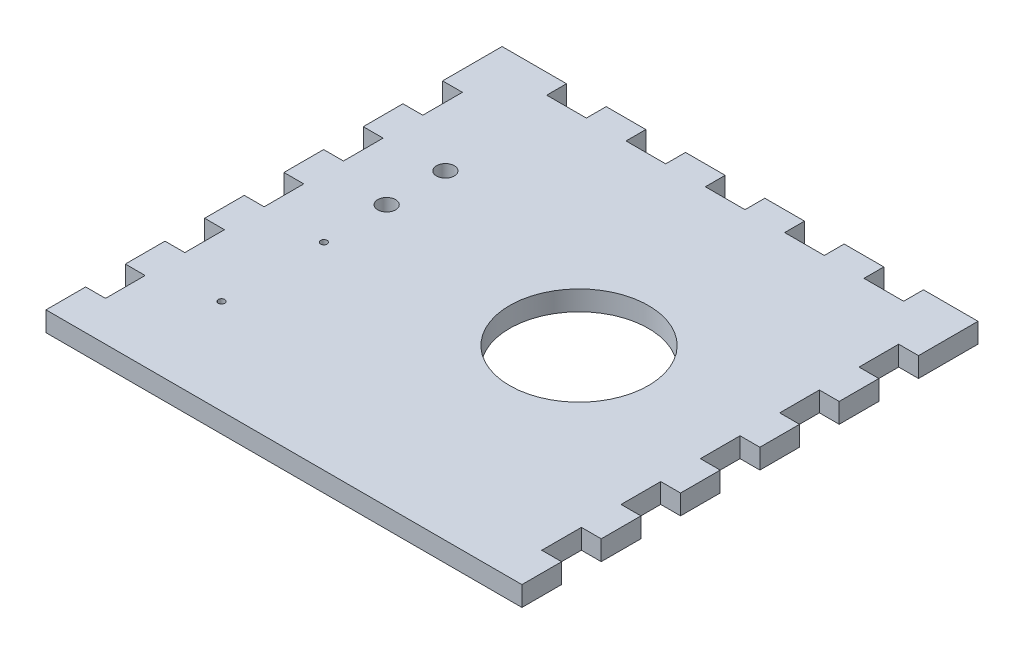
SolidWorks part; units mm, degrees
ref_plane "Front Plane" through (0, 0, 0) normal (0, 0, 1) x (1, 0, 0)
ref_plane "Top Plane" through (0, 0, 0) normal (0, 1, 0) x (1, 0, 0)
ref_plane "Right Plane" through (0, 0, 0) normal (1, 0, 0) x (0, 0, -1)
sketch "Sketch1" plane through (0, 0, 0) normal (0, 1, 0) x (1, 0, 0)
  line L1 (-139.7, -139.7) -> (139.7, -139.7)
  line L2 (-139.7, -139.7) -> (-139.7, 139.7)
  line L3 (-139.7, 139.7) -> (139.7, 139.7)
  line L4 (139.7, -139.7) -> (139.7, 139.7)
  line L5 (-139.7, -139.7) -> (139.7, 139.7) construction
  line L6 (-139.7, 139.7) -> (139.7, -139.7) construction
  point P0 (0, 0)
  dimension "D1" = 279.4
  dimension "D2" = 279.4
extrude "Boss-Extrude1" add sketch "Sketch1" along normal blind 12.7
sketch "Sketch2" plane through (139.7, 0, 0) normal (1, 0, 0) x (0, 0, -1)
  line L0 (-139.7, 12.7) -> (139.7, 12.7) construction
  line L1 (-139.7, 0) -> (-114.3, 0)
  line L2 (-139.7, 0) -> (-139.7, 12.7)
  line L3 (-139.7, 12.7) -> (-114.3, 12.7)
  line L4 (-114.3, 0) -> (-114.3, 12.7)
  dimension "D1" = 25.4
extrude "Boss-Extrude2" add sketch "Sketch2" along normal blind 12.7
pattern_linear "LPattern1" count 6 spacing 50.8 along (0, 0, -1) of "Boss-Extrude2"
mirror "Mirror1" about plane through (0, 0, 0) normal (1, 0, 0) of "LPattern1"
sketch "Sketch3" plane through (0, 0, -139.7) normal (0, 0, -1) x (-1, 0, 0)
  line L0 (-152.4, 12.7) -> (152.4, 12.7) construction
  line L1 (-142.875, 12.7) -> (-117.475, 12.7)
  line L2 (-142.875, 12.7) -> (-142.875, 0)
  line L3 (-142.875, 0) -> (-117.475, 0)
  line L4 (-117.475, 12.7) -> (-117.475, 0)
  line L5 (-152.4, 0) -> (152.4, 0) construction
  line L6 (-152.4, 0) -> (-152.4, 12.7) construction
  dimension "D1" = 9.525
  dimension "D2" = 25.4
extrude "Boss-Extrude3" add sketch "Sketch3" along normal blind 12.7
pattern_linear "LPattern2" count 6 spacing 50.8 along (-1, 0, 0) of "Boss-Extrude3"
sketch "Sketch5" plane through (0, 0, -139.7) normal (0, 0, -1) x (-1, 0, 0)
  line L6 (160.655, 0) -> (-160.655, 0) construction
  line L7 (-152.4, 12.7) -> (-135.3964, 12.7)
  line L8 (-152.4, 12.7) -> (-152.4, 0)
  line L9 (-152.4, 0) -> (-135.3964, 0)
  line L10 (-135.3964, 12.7) -> (-135.3964, 0)
extrude "Boss-Extrude4" add sketch "Sketch5" along normal blind 12.7
mirror "Mirror2" about plane through (0, 0, 0) normal (1, 0, 0) of "Boss-Extrude4"
sketch "Sketch6" plane through (0, 12.7, 0) normal (0, 1, 0) x (1, 0, 0)
  line L0 (66.675, 139.7) -> (41.275, 139.7) construction
  line L1 (139.7, -12.7) -> (139.7, 12.7) construction
  circle A0 centre (38.1, 11.176) radius 44.45
  dimension "D1" = 128.524
  dimension "D2" = 101.6
extrude "Cut-Extrude1" cut sketch "Sketch6" against normal through all
sketch "Sketch7" plane through (0, 12.7, 0) normal (0, 1, 0) x (1, 0, 0)
  line L0 (-139.7, 63.5) -> (-139.7, 38.1) construction
  line L1 (-139.7, 114.3) -> (-139.7, 88.9) construction
  line L2 (-85.725, 139.7) -> (-111.125, 139.7) construction
  circle A0 centre (-101.6, 65.278) radius 5.715
  circle A1 centre (-101.6, 27.686) radius 5.715
  dimension "D1" = 11.43
  dimension "D2" = 11.43
  dimension "D3" = 38.1
  dimension "D4" = 38.1
  dimension "D5" = 37.592
  dimension "D6" = 74.422
extrude "Cut-Extrude2" cut sketch "Sketch7" against normal through all
sketch "Sketch8" plane through (0, 12.7, 0) normal (0, 1, 0) x (1, 0, 0)
  circle A0 centre (-100.9, -78.8111) radius 2.1 construction
  circle A1 centre (-100.9, -78.8111) radius 2.1
  circle A2 centre (-100.9, -13.2039) radius 2.1 construction
  circle A3 centre (-100.9, -13.2039) radius 2.1
extrude "Cut-Extrude3" cut sketch "Sketch8" against normal through all
